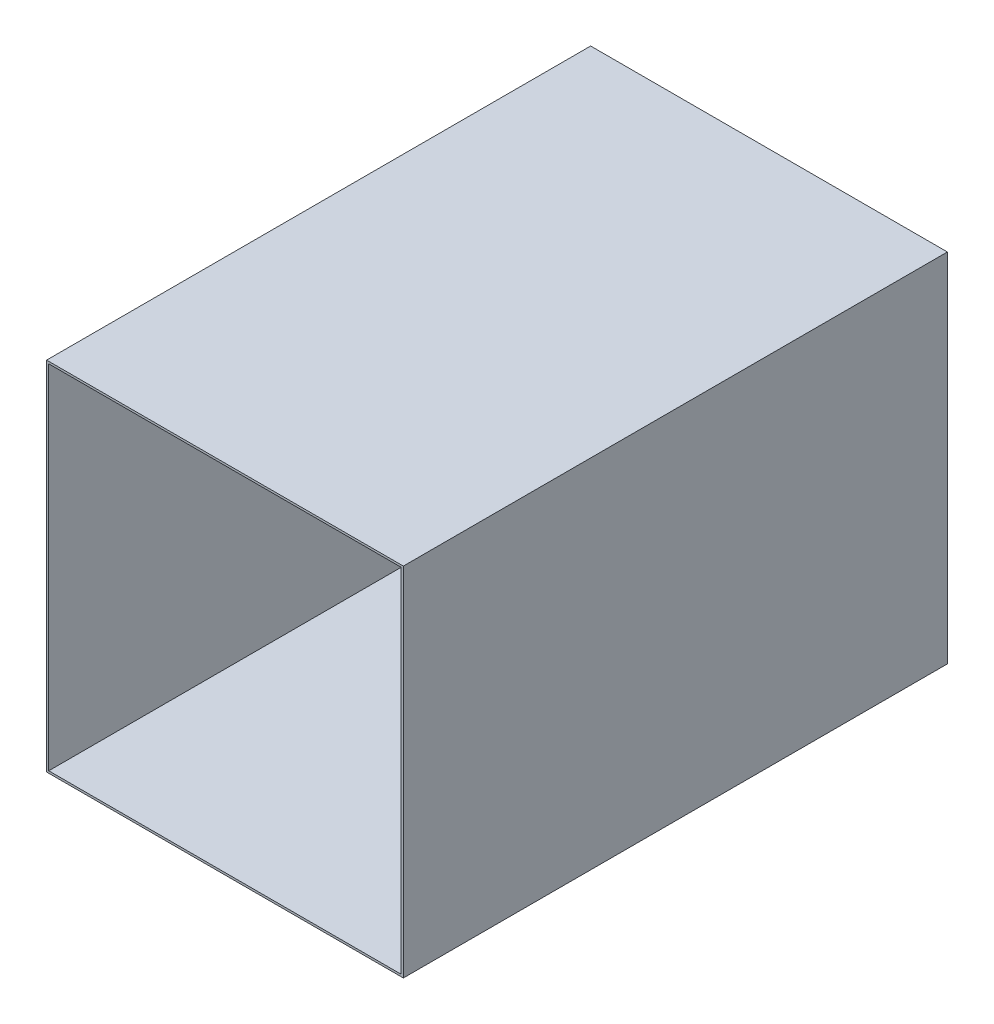
SolidWorks part; units mm, degrees
material "6061-T6 (SS)"
ref_plane "Front" through (0, 0, 0) normal (0, 0, 1) x (1, 0, 0)
ref_plane "Top" through (0, 0, 0) normal (0, 1, 0) x (1, 0, 0)
ref_plane "Right" through (0, 0, 0) normal (1, 0, 0) x (0, 0, -1)
sketch "Sketch1" plane through (0, 0, 0) normal (0, 0, 1) x (1, 0, 0)
  line L0 (-247, 3) -> (-247, 497)
  line L1 (-250, 0) -> (250, 0)
  line L2 (-250, 0) -> (-250, 500)
  line L3 (-250, 500) -> (250, 500)
  line L4 (250, 0) -> (250, 500)
  line L5 (-247, 497) -> (247, 497)
  line L6 (247, 3) -> (247, 497)
  line L7 (-247, 3) -> (247, 3)
  dimension "D1" = 500
  dimension "D2" = 3
extrude "Boss-Extrude1" add sketch "Sketch1" along normal blind 762.5
